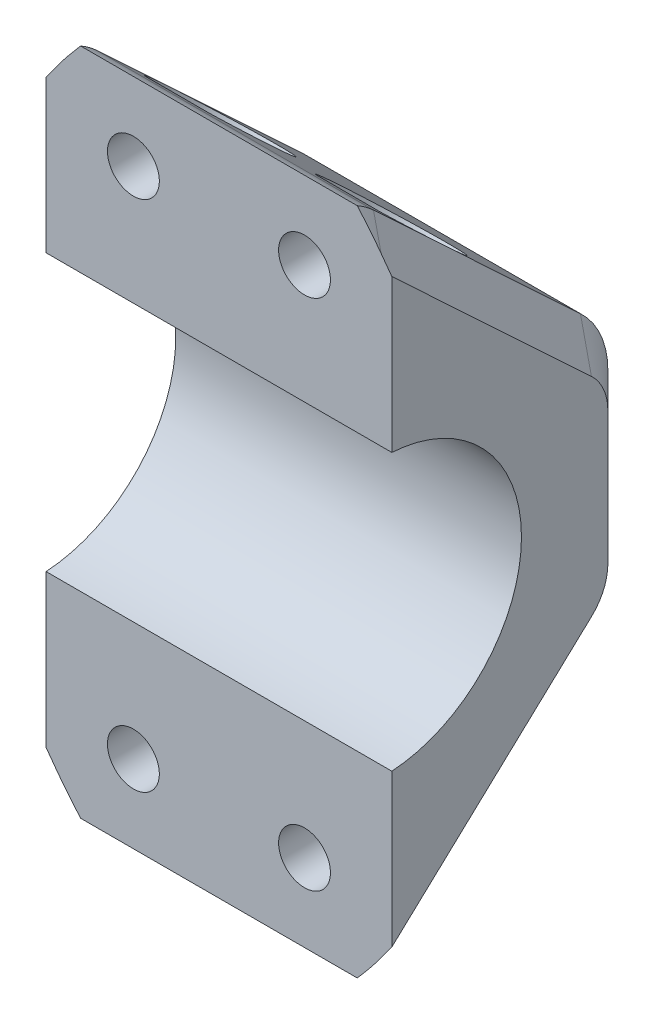
SolidWorks part; units mm, degrees
material "ABS"
ref_plane "Front Plane" through (0, 0, 0) normal (0, 0, 1) x (1, 0, 0)
ref_plane "Top Plane" through (0, 0, 0) normal (0, 1, 0) x (1, 0, 0)
ref_plane "Right Plane" through (0, 0, 0) normal (1, 0, 0) x (0, 0, -1)
sketch "Sketch1" plane through (0, 0, 0) normal (0, 0, 1) x (1, 0, 0)
  line L8 (10.6892, 89.7411) -> (30.6892, 89.7411)
  line L9 (30.6892, 89.7411) -> (30.6892, 139.3411)
  line L10 (30.6892, 139.3411) -> (10.6892, 139.3411)
  line L11 (10.6892, 139.3411) -> (10.6892, 89.7411)
  circle A4 centre (15.7395, 99.6914) radius 1.5
  circle A5 centre (25.639, 99.6914) radius 1.5
  circle A6 centre (25.639, 129.3909) radius 1.5
  circle A7 centre (15.7395, 129.3909) radius 1.5
sketch "Sketch2" plane through (0, 0, 0) normal (0, 0, 1) x (1, 0, 0)
  line L0 (10.6892, 89.7411) -> (30.6892, 89.7411) construction
  line L1 (30.6892, 89.7411) -> (30.6892, 139.3411) construction
  line L2 (10.6892, 139.3411) -> (10.6892, 89.7411) construction
  line L3 (30.6892, 139.3411) -> (10.6892, 139.3411) construction
  line L4 (10.6892, 89.7411) -> (30.6892, 89.7411)
  line L5 (30.6892, 89.7411) -> (30.6892, 139.3411)
  line L6 (10.6892, 139.3411) -> (10.6892, 89.7411)
  line L7 (30.6892, 139.3411) -> (10.6892, 139.3411)
  circle A0 centre (15.7395, 99.6914) radius 1.5 construction
  circle A1 centre (25.639, 99.6914) radius 1.5 construction
  circle A2 centre (25.639, 129.3909) radius 1.5 construction
  circle A3 centre (15.7395, 129.3909) radius 1.5 construction
  circle A4 centre (15.7395, 99.6914) radius 1.5
  circle A5 centre (25.639, 99.6914) radius 1.5
  circle A6 centre (25.639, 129.3909) radius 1.5
  circle A7 centre (15.7395, 129.3909) radius 1.5
extrude "Boss-Extrude1" add sketch "Sketch2" along normal blind 30
sketch "Sketch3" plane through (30.6892, 0, 0) normal (1, 0, 0) x (0, 0, -1)
  line L0 (-30, 139.3411) -> (0, 89.7411)
  line L2 (-20, 109.5411) -> (-10, 109.5411)
  line L3 (-20, 109.5411) -> (-20, 119.5411)
  line L4 (0, 89.7411) -> (0, 139.3411)
  line L5 (0, 139.3411) -> (-30, 139.3411)
  line L6 (-30, 139.3411) -> (-30, 89.7411)
  line L7 (-30, 89.7411) -> (0, 89.7411)
  line L8 (0, 89.7411) -> (0, 139.3411)
  line L9 (0, 139.3411) -> (-30, 139.3411)
  line L10 (-30, 139.3411) -> (-30, 89.7411)
  line L11 (-30, 89.7411) -> (0, 89.7411)
  line L12 (-20, 119.5411) -> (-10, 119.5411)
  line L13 (-10, 109.5411) -> (-10, 119.5411)
  line L14 (-20, 109.5411) -> (-10, 119.5411) construction
  line L15 (-20, 119.5411) -> (-10, 109.5411) construction
  point P2 (-15, 114.5411)
  dimension "D2" = 10
  dimension "D1" = 0
extrude "Cut-Extrude1" cut sketch "Sketch3" against normal blind 30 contours L2 L13 L12 L0 | L12 L3 L2 L0 region at (30.6892, 115.5492, 12.8049) region at (30.6892, 113.533, 17.1951)
sketch "Sketch4" plane through (30.6892, 0, 0) normal (1, 0, 0) x (0, 0, -1)
  line L0 (0, 89.7411) -> (-30, 139.3411)
  line L1 (0, 120.5411) -> (0, 108.5411)
  line L2 (-30, 134.5411) -> (0, 134.5411)
  line L3 (-30, 134.5411) -> (-30, 94.5411)
  line L4 (0, 89.7411) -> (0, 139.3411)
  line L5 (0, 139.3411) -> (-30, 139.3411)
  line L6 (-30, 139.3411) -> (-30, 89.7411)
  line L7 (-30, 89.7411) -> (0, 89.7411)
  line L8 (0, 89.7411) -> (0, 139.3411)
  line L9 (0, 139.3411) -> (-30, 139.3411)
  line L10 (-30, 139.3411) -> (-30, 89.7411)
  line L11 (-30, 89.7411) -> (0, 89.7411)
  line L12 (-30, 94.5411) -> (0, 94.5411)
  line L13 (0, 134.5411) -> (0, 94.5411)
  line L14 (-30, 134.5411) -> (0, 94.5411) construction
  line L15 (-30, 94.5411) -> (0, 134.5411) construction
  line L16 (-15, 134.5411) -> (0, 120.5411)
  line L17 (-30, 114.5411) -> (0, 114.5411)
  line L18 (-15, 94.5411) -> (0, 108.5411)
  point P2 (-15, 114.5411)
  point P13 (0, 114.5411)
  line M16 (0, 89.7411) -> (0, 139.3411)
  line M17 (0, 139.3411) -> (-30, 139.3411)
  line M18 (-30, 139.3411) -> (-30, 89.7411)
  line M19 (-30, 89.7411) -> (0, 89.7411)
  dimension "D2" = 40
  dimension "D3" = 12
  dimension "D1" = 0
extrude "Cut-Extrude2" cut sketch "Sketch4" against normal blind 22 contours L0 L2 M16 M17 | L2 L0 M18 | L2 L16 M16 | L18 L0 L12 L8 | L18 L12 L0 | L12 L0 M18 M19 | L12 L0 M16 region at (30.6892, 92.1004, 15.7135) region at (30.6892, 92.9411, 0.9677) region at (30.6892, 96.9466, 8.3904) region at (30.6892, 100.8165, 2.5879) region at (30.6892, 136.1411, 29.0323) region at (30.6892, 136.9818, 14.2865) region at (30.6892, 129.8744, 5)
fillet "Fillet1" radius 5 4 edges at (20.6892, 134.5411, 15) (20.6892, 94.5411, 15) (20.6892, 120.5411, 0) (20.6892, 108.5411, 0)
fillet "Fillet2" radius 2 2 edges at (20.6892, 94.5411, 30) (20.6892, 134.5411, 30)
chamfer "Chamfer1" distance 2 angle 45 24 edges at (30.6892, 134.5411, 22.4854) (30.6892, 133.9553, 29.4142) (30.6892, 134.1928, 15.1373) (30.6892, 114.5411, 30) (30.6892, 127.61, 7.5738) (30.6892, 95.1269, 29.4142) (30.6892, 120.3611, 0.4143) (30.6892, 94.5411, 22.4854) (30.6892, 114.5411, 0) (30.6892, 94.8894, 15.1373) (30.6892, 108.7211, 0.4143) (30.6892, 101.4722, 7.5738) (10.6892, 134.5411, 22.4854) (10.6892, 133.9553, 29.4142) (10.6892, 134.1928, 15.1373) (10.6892, 114.5411, 30) (10.6892, 127.61, 7.5738) (10.6892, 95.1269, 29.4142) (10.6892, 120.3611, 0.4143) (10.6892, 94.5411, 22.4854) (10.6892, 114.5411, 0) (10.6892, 94.8894, 15.1373) (10.6892, 108.7211, 0.4143) (10.6892, 101.4722, 7.5738)
sketch "Sketch5" plane through (0, 0, 0) normal (0, 0, -1) x (-1, 0, 0)
  circle A0 centre (-15.7395, 129.3909) radius 1.5 construction
  circle A1 centre (-25.639, 129.3909) radius 1.5 construction
  circle A2 centre (-25.639, 99.6914) radius 1.5 construction
  circle A3 centre (-15.7395, 99.6914) radius 1.5 construction
  circle A4 centre (-15.7395, 129.3909) radius 1.5
  circle A5 centre (-25.639, 129.3909) radius 1.5
  circle A6 centre (-25.639, 99.6914) radius 1.5
  circle A7 centre (-15.7395, 99.6914) radius 1.5
  circle A8 centre (-15.7395, 99.6914) radius 3
  circle A9 centre (-25.639, 99.6914) radius 3
  circle A10 centre (-15.7395, 129.3909) radius 3
  circle A11 centre (-25.639, 129.3909) radius 3
  dimension "D1" = 1.5
extrude "Cut-Extrude3" cut sketch "Sketch5" against normal blind 12
sketch "Sketch6" plane through (10.6892, 0, 0) normal (-1, 0, 0) x (0, 0, 1)
  line L0 (10, 109.5411) -> (20, 119.5411)
  line L1 (15, 137.8794) -> (15, 91.2028)
  line L2 (16, 137.8794) -> (16, 91.2028)
  line L3 (16, 137.8794) -> (16, 91.2028)
  line L4 (16, 137.8794) -> (-6.9537, 137.8794)
  line L5 (16, 91.2028) -> (-6.9537, 91.2028)
  line L6 (-6.9537, 137.8794) -> (-6.9537, 91.2028)
  line L7 (16, 137.8794) -> (16, 91.2028)
  line L8 (16, 137.8794) -> (39.9105, 137.8794)
  line L9 (16, 91.2028) -> (39.9105, 91.2028)
  line L10 (39.9105, 137.8794) -> (39.9105, 91.2028)
  line L11 (14.5, 137.8794) -> (14.5, 91.2028)
  circle A0 centre (15, 114.5411) radius 8
  point P9 (15, 114.5411)
  line M2 (28, 96.5411) -> (28, 132.5411)
  line M3 (28, 132.5411) -> (16.9708, 132.5411)
  arc M4 (16.9708, 132.5411) -> (14.9239, 131.7343) centre (16.9708, 129.5411) ccw
  line M5 (14.9239, 131.7343) -> (2.953, 120.5615)
  line M9 (2.953, 108.5207) -> (14.9239, 97.3479)
  arc M10 (14.9239, 97.3479) -> (16.9708, 96.5411) centre (16.9708, 99.5411) ccw
  line M11 (16.9708, 96.5411) -> (28, 96.5411)
  line M12 (20, 119.5411) -> (20, 109.5411)
  line M13 (20, 109.5411) -> (10, 109.5411)
  line M14 (10, 109.5411) -> (10, 119.5411)
  line M15 (10, 119.5411) -> (20, 119.5411)
  dimension "D1" = 16
  dimension "D2" = 1
  dimension "D3" = 0.5
extrude "Cut-Extrude4" cut sketch "Sketch6" against normal blind 23 contours L10 L8 L2 L9 M4 M3 M2 M11 M10 | A0 L7 L2 M10 M11 M2 M3 M4 | L0 L2 M13 M12 | L2 L0 M15 | L11 A0 M13 M14 M15 | L2 A0 L7 M15 M12 M13 | L11 L0 M15 M14 | L1 A0 L11 M15 | L7 A0 L1 M15 | L11 L0 L1 M15 | L2 L1 L0 M15 | L11 L0 M13 | L0 L11 L1 M13 | L2 L0 L1 M13 | L11 A0 L1 M13 | L1 A0 L2 M13 | A0 L11 L1 M9 M10 | A0 L1 L7 M10 | L11 L5 L1 M9 M10 | L5 L2 L1 M10 | A0 L1 L11 M4 M5 | A0 L2 L1 M4 | L4 L11 L1 M5 M4 | L2 L4 L1 M4 region at (10.6892, 115.5572, 12.0323) region at (10.6892, 111.0411, 13) region at (10.6892, 109.3647, 12.25) region at (10.6892, 116.9141, 14.746) region at (10.6892, 111.9183, 14.7544) region at (10.6892, 108.0437, 14.7502) region at (10.6892, 117.2818, 15.4815) region at (10.6892, 112.2987, 15.5152) region at (10.6892, 121.0385, 14.7502) region at (10.6892, 102.0273, 14.7521) region at (10.6892, 108.0515, 15.4982) region at (10.6892, 118.2078, 17.3333) region at (10.6892, 113.6244, 18.1667) region at (10.6892, 121.0307, 15.4982) region at (10.6892, 127.0549, 14.7521) region at (10.6892, 94.358, 14.7469) region at (10.6892, 101.7534, 15.5055) region at (10.6892, 109.3676, 18) region at (10.6892, 127.3288, 15.5055) region at (10.6892, 134.7242, 14.7469) region at (10.6892, 94.0777, 15.4917) region at (10.6892, 108.9986, 21.2846) region at (10.6892, 135.0046, 15.4917) region at (10.6892, 114.5411, 31.7138)
